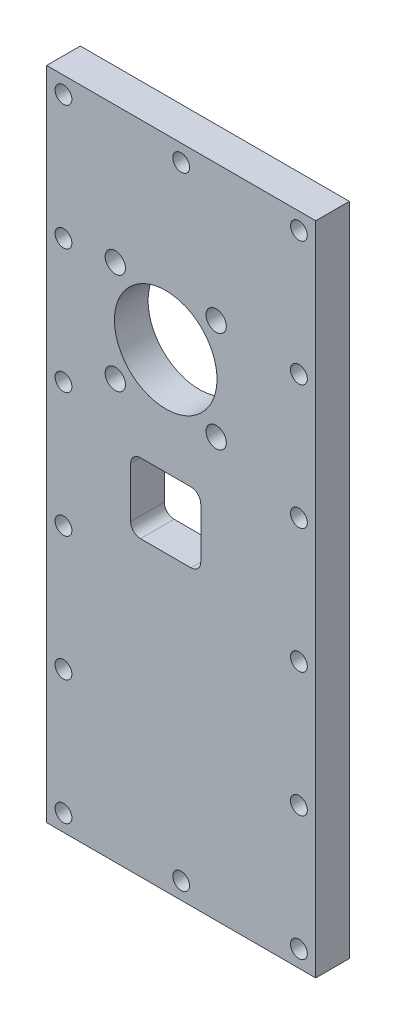
SolidWorks part; units mm, degrees
ref_plane "Ebene vorne" through (0, 0, 0) normal (0, 0, 1) x (1, 0, 0)
ref_plane "Ebene oben" through (0, 0, 0) normal (0, 1, 0) x (1, 0, 0)
ref_plane "Ebene rechts" through (0, 0, 0) normal (1, 0, 0) x (0, 0, -1)
sketch "Skizze1" plane through (0, 0, 0) normal (0, 0, 1) x (1, 0, 0)
  line L1 (-69.0594, 70.0995) -> (10.9406, 70.0995)
  line L2 (-69.0594, 70.0995) -> (-69.0594, -124.9005)
  line L3 (-69.0594, -124.9005) -> (10.9406, -124.9005)
  line L4 (10.9406, 70.0995) -> (10.9406, -124.9005)
  dimension "D1" = 195
  dimension "D2" = 80
extrude "Aufsatz-Linear austragen1" add sketch "Skizze1" against normal blind 10
sketch "Skizze2" plane through (0, 0, -10) normal (0, 0, -1) x (-1, 0, 0)
  line L0 (69.0594, 70.0995) -> (69.0594, -124.9005) construction
  line L1 (33.6594, 14.5995) -> (33.6594, -27.4005) construction
  line L3 (33.6594, 14.5995) -> (69.0594, 14.5995) construction
  line L5 (18.6594, 29.5995) -> (48.6594, 29.5995) construction
  line L6 (48.6594, 29.5995) -> (48.6594, -0.4005) construction
  line L7 (48.6594, -0.4005) -> (18.6594, -0.4005) construction
  line L8 (18.6594, -0.4005) -> (18.6594, 29.5995) construction
  line L9 (18.6594, 29.5995) -> (48.6594, -0.4005) construction
  line L10 (69.0594, -27.4005) -> (-10.9406, -27.4005) construction
  line L11 (-10.9406, -124.9005) -> (-10.9406, 70.0995) construction
  line L12 (23.2413, -19.9005) -> (23.2413, -34.9005)
  line L13 (26.1594, -16.9824) -> (41.1594, -16.9824)
  line L14 (44.0774, -19.9005) -> (44.0774, -34.9005)
  line L15 (41.1594, -37.8185) -> (26.1594, -37.8185)
  line L16 (23.2413, -19.9005) -> (44.0774, -34.9005) construction
  line L17 (26.1594, -37.8185) -> (41.1594, -16.9824) construction
  circle A0 centre (18.6594, 29.5995) radius 3.015
  circle A1 centre (48.6594, 29.5995) radius 3.015
  circle A2 centre (18.6594, -0.4005) radius 3.015
  circle A3 centre (48.6594, -0.4005) radius 3.015
  circle A4 centre (33.6594, 14.5995) radius 15.25
  arc A5 (23.2413, -19.9005) -> (26.1594, -16.9824) centre (26.1594, -19.9005) cw
  arc A6 (41.1594, -16.9824) -> (44.0774, -19.9005) centre (41.1594, -19.9005) cw
  arc A7 (44.0774, -34.9005) -> (41.1594, -37.8185) centre (41.1594, -34.9005) cw
  arc A8 (26.1594, -37.8185) -> (23.2413, -34.9005) centre (26.1594, -34.9005) cw
  point P22 (33.6594, 14.5995)
  point P32 (33.6594, -27.4005)
  dimension "D1" = 30
  dimension "D3" = 6.03
  dimension "D2" = 30
  dimension "D4" = 35.4
  dimension "D5" = 42
  dimension "D6" = 15
extrude "Schnitt-Linear austragen1" cut sketch "Skizze2" against normal blind 10
sketch "Skizze3" plane through (0, 0, -10) normal (0, 0, -1) x (-1, 0, 0)
  line L0 (-5.9406, 65.0995) -> (63.8159, 65.0995) construction
  line L1 (63.8159, 65.0995) -> (63.8159, 28.0995) construction
  line L2 (63.8159, 28.0995) -> (63.8159, -8.9005) construction
  line L3 (63.8159, -8.9005) -> (63.8159, -45.9005) construction
  line L4 (63.8159, -45.9005) -> (63.8159, -82.9005) construction
  line L5 (63.8159, -82.9005) -> (63.8159, -119.9005) construction
  line L6 (63.8159, -119.9005) -> (-5.9406, -119.9005) construction
  line L7 (-5.9406, -119.9005) -> (-5.9406, -82.9005) construction
  line L8 (-5.9406, -82.9005) -> (-5.9406, -45.9005) construction
  line L9 (-5.9406, -45.9005) -> (-5.9406, -8.9005) construction
  line L10 (-5.9406, -8.9005) -> (-5.9406, 28.0995) construction
  line L11 (-5.9406, 28.0995) -> (-5.9406, 65.0995) construction
  line L12 (28.9377, 65.0995) -> (29.0594, 70.0995) construction
  line L13 (-10.9406, 70.0995) -> (69.0594, 70.0995) construction
  line L14 (28.9377, -119.9005) -> (29.0594, -124.9005) construction
  line L15 (69.0594, -124.9005) -> (-10.9406, -124.9005) construction
  line L16 (-10.9406, -124.9005) -> (-10.9406, 70.0995) construction
  circle A0 centre (-5.9406, 65.0995) radius 1.25
  circle A1 centre (63.8159, 65.0995) radius 1.25
  circle A2 centre (28.9377, 65.0995) radius 1.25
  circle A3 centre (63.8159, 28.0995) radius 1.25
  circle A4 centre (63.8159, -8.9005) radius 1.25
  circle A5 centre (63.8159, -45.9005) radius 1.25
  circle A6 centre (63.8159, -82.9005) radius 1.25
  circle A7 centre (63.8159, -119.9005) radius 1.25
  circle A8 centre (28.9377, -119.9005) radius 1.25
  circle A9 centre (-5.9406, -119.9005) radius 1.25
  circle A10 centre (-5.9406, -82.9005) radius 1.25
  circle A11 centre (-5.9406, -45.9005) radius 1.25
  circle A12 centre (-5.9406, -8.9005) radius 1.25
  circle A13 centre (-5.9406, 28.0995) radius 1.25
  dimension "D4" = 2.5
  dimension "D1" = 5
  dimension "D2" = 5
  dimension "D3" = 5
extrude "Schnitt-Linear austragen2" cut sketch "Skizze3" against normal blind 5
sketch "Skizze4" plane through (0, 0, 0) normal (0, 0, 1) x (1, 0, 0)
  line L0 (5.9406, 65.0995) -> (5.9406, 28.0995) construction
  line L1 (5.9406, 28.0995) -> (5.9406, -8.9005) construction
  line L2 (5.9406, -8.9005) -> (5.9406, -45.9005) construction
  line L3 (5.9406, -45.9005) -> (5.9406, -82.9005) construction
  line L4 (5.9406, -82.9005) -> (5.9406, -119.9005) construction
  line L5 (5.9406, -119.9005) -> (-64.0594, -119.9005) construction
  line L6 (-64.0594, -119.9005) -> (-64.0594, -82.9005) construction
  line L7 (-64.0594, -82.9005) -> (-64.0594, -45.9005) construction
  line L8 (-64.0594, -45.9005) -> (-64.0594, -8.9005) construction
  line L9 (-64.0594, -8.9005) -> (-64.0594, 28.0995) construction
  line L10 (-64.0594, 28.0995) -> (-64.0594, 65.0995) construction
  line L11 (-64.0594, 65.0995) -> (5.9406, 65.0995) construction
  line L12 (-29.0594, 65.0995) -> (-29.0594, 70.0995) construction
  line L13 (10.9406, 70.0995) -> (-69.0594, 70.0995) construction
  line L14 (-69.0594, 70.0995) -> (-69.0594, -124.9005) construction
  line L15 (-69.0594, -124.9005) -> (10.9406, -124.9005) construction
  circle A0 centre (-64.0594, 65.0995) radius 2.5
  circle A1 centre (5.9406, 65.0995) radius 2.5
  circle A2 centre (5.9406, 28.0995) radius 2.5
  circle A3 centre (5.9406, -8.9005) radius 2.5
  circle A4 centre (5.9406, -45.9005) radius 2.5
  circle A5 centre (5.9406, -82.9005) radius 2.5
  circle A6 centre (5.9406, -119.9005) radius 2.5
  circle A7 centre (-64.0594, -119.9005) radius 2.5
  circle A8 centre (-64.0594, -82.9005) radius 2.5
  circle A9 centre (-64.0594, -45.9005) radius 2.5
  circle A10 centre (-64.0594, -8.9005) radius 2.5
  circle A11 centre (-64.0594, 28.0995) radius 2.5
  circle A12 centre (-29.0594, -119.9005) radius 2.5
  circle A13 centre (-29.0594, 65.0995) radius 2.5
  dimension "D4" = 5
  dimension "D1" = 5
  dimension "D2" = 5
  dimension "D3" = 5
extrude "Schnitt-Linear austragen3" cut sketch "Skizze4" against normal blind 5
